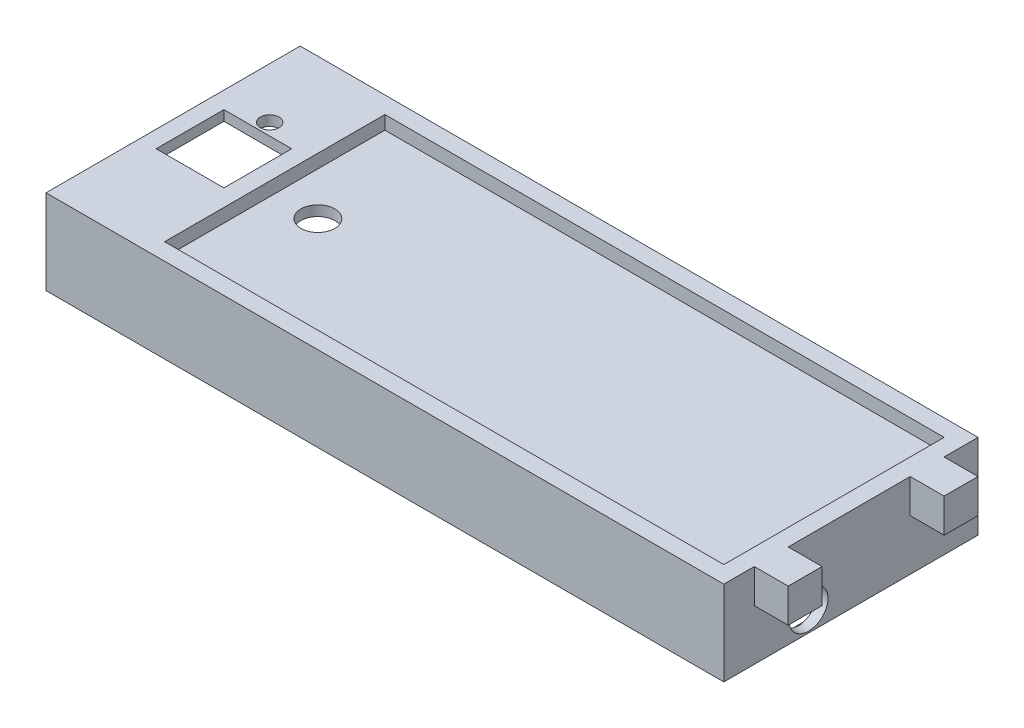
SolidWorks part; units mm, degrees
ref_plane "Front Plane" through (0, 0, 0) normal (0, 0, 1) x (1, 0, 0)
ref_plane "Top Plane" through (0, 0, 0) normal (0, 1, 0) x (1, 0, 0)
ref_plane "Right Plane" through (0, 0, 0) normal (1, 0, 0) x (0, 0, -1)
sketch "Sketch1" plane through (0, 0, 0) normal (0, 1, 0) x (1, 0, 0)
  line L1 (-60, 37.5) -> (140, 37.5)
  line L2 (-60, 37.5) -> (-60, -37.5)
  line L3 (-60, -37.5) -> (140, -37.5)
  line L4 (140, 37.5) -> (140, -37.5)
  point P0 (0, 0)
  dimension "D1" = 200
  dimension "D2" = 75
extrude "Boss-Extrude1" add sketch "Sketch1" along normal blind 25
sketch "Sketch9" plane through (0, 25, 0) normal (0, 1, 0) x (1, 0, 0)
  line L1 (-30, 32.5) -> (135, 32.5)
  line L2 (-30, 32.5) -> (-30, -32.5)
  line L3 (-30, -32.5) -> (135, -32.5)
  line L4 (135, 32.5) -> (135, -32.5)
  line L5 (140, -37.5) -> (140, 37.5) construction
  point P4 (135, 0)
  dimension "D1" = 165
  dimension "D2" = 65
  dimension "D3" = 0
  dimension "D4" = 5
extrude "Cut-Extrude5" cut sketch "Sketch9" against normal blind 4
shell "Shell3" thickness 3 removed face at (40, 0, 0) removed face at (-60, 12.5, 0)
sketch "Sketch14" plane through (140, 0, 0) normal (1, 0, 0) x (0, 0, -1)
  line L0 (37.5, 25) -> (37.5, 0) construction
  line L1 (-28.5, 25) -> (-18.5, 25)
  line L2 (-28.5, 25) -> (-28.5, 15)
  line L3 (-28.5, 15) -> (-18.5, 15)
  line L4 (-18.5, 25) -> (-18.5, 15)
  line L5 (17.5, 25) -> (27.5, 25)
  line L6 (17.5, 25) -> (17.5, 15)
  line L7 (17.5, 15) -> (27.5, 15)
  line L8 (27.5, 25) -> (27.5, 15)
  line L9 (-37.5, 25) -> (37.5, 25) construction
  dimension "D1" = 10
  dimension "D2" = 10
  dimension "D3" = 10
  dimension "D4" = 36
extrude "Boss-Extrude5" add sketch "Sketch14" along normal blind 10
sketch "Sketch15" plane through (0, 21, 0) normal (0, 1, 0) x (1, 0, 0)
  circle A0 centre (-17.2823, 0) radius 5
extrude "Cut-Extrude7" cut sketch "Sketch15" against normal through all
sketch "Sketch16" plane through (0, 25, 0) normal (0, 1, 0) x (1, 0, 0)
  line L0 (-30, 32.5) -> (-30, -32.5) construction
  line L1 (-55, -10) -> (-35, -10)
  line L2 (-55, -10) -> (-55, 10)
  line L3 (-55, 10) -> (-35, 10)
  line L4 (-35, -10) -> (-35, 10)
  line L5 (-55, -10) -> (-35, 10) construction
  line L6 (-55, 10) -> (-35, -10) construction
  line L7 (-60, -37.5) -> (140, -37.5) construction
  line L8 (140, 37.5) -> (-60, 37.5) construction
  point P0 (-45, 0)
  dimension "D1" = 20
  dimension "D2" = 20
  dimension "D3" = 5
  dimension "D4" = 27.5
  dimension "D5" = 27.5
extrude "Cut-Extrude8" cut sketch "Sketch16" against normal through all
ref_plane "Plane1" through (0, 0, 0) normal (0, 0, -1) x (-1, 0, 0)
sketch "Sketch19" plane through (140, 0, 0) normal (1, 0, 0) x (0, 0, -1)
  line L1 (-37.5, 0) -> (37.5, 0) construction
  line L3 (-37.5, 25) -> (-37.5, 0) construction
  ellipse E0 centre (-12.5, 6) end of major axis (-6.75, 6) minor radius 5.5
  dimension "D1" = 6
  dimension "D2" = 25
  dimension "D3" = 11.5
  dimension "D4" = 11
sketch "Sketch20" plane through (0, 0, 0) normal (0, 0, -1) x (-1, 0, 0)
  line L1 (-137, 18) -> (-137, 0) construction
  spline S0 degree 2 poles (-140, 6) (-136.1989, 6.6303) (-133.0758, 4.1829) knots 0 0 0 1 1 1
sweep "Cut-Sweep2" cut profiles "Sketch19" path "Sketch20"
sketch "Sketch21" plane through (0, 25, 0) normal (0, 1, 0) x (1, 0, 0)
  line L0 (-55, 0) -> (-35, 0)
  line L1 (-55, 10) -> (-55, -10) construction
  line L2 (-35, -10) -> (-35, 10) construction
  line L3 (-45, 0) -> (-45, 13.5)
  circle A0 centre (-45, 13.5) radius 2.75
  dimension "D2" = 5.5
  dimension "D1" = 13.5
extrude "Cut-Extrude9" cut sketch "Sketch21" against normal through all contours A0
sketch3d "3DSketch1"
  line L0 (-60, 0, 34.5) -> (-60, 6, 34.5) construction
  line L1 (-60, 22, 34.5) -> (-60, 0, 34.5) construction
  line L2 (-60, 6, 34.5) -> (-60, 6, 32.7) construction
  line L3 (-60, 6, 32.7) -> (-56.4756, 6, 32.7) construction
  line L4 (-56.4756, 6, 32.7) -> (126.5244, 6, 32.7) construction
  line L5 (126.5244, 6, 32.7) -> (131.5244, 6, 32.7) construction
  line L6 (131.5244, 6, 32.7) -> (131.5244, 6, 27.5033) construction
  line L7 (131.5244, 6, 27.5033) -> (131.5244, 6, 16.563) construction
  line L8 (-60, 6, 32.7) -> (-60, 6, 27.3188) construction
  line L9 (-60, 6, 27.3188) -> (-60, 6, 27.5805)
  line L10 (-60, 6, 27.5805) -> (-60, 6, -4.2159)
  point P13 (134.1316, 6, 11.9486)
  point P14 (134.2201, 6, 16.563)
  point P15 (131.0244, 6, 32.7)
  dimension "D2" = 1.8
  dimension "D1" = 6
  dimension "183" = 183
  dimension "D3" = 5
ref_axis "Axis1" through (-56.4756, 6, 32.7) along (1, 0, 0)
other "RPoint1"
other "RPoint2"
ref_axis "Axis2" through (131.5244, 6, 27.5033) along (0, 0, -1)
other "RPoint3"
other "RPoint4"
ref_axis "Axis3" through (-60, 6, 27.5805) along (0, 0, -1)
other "RPoint5"
other "RPoint6"
